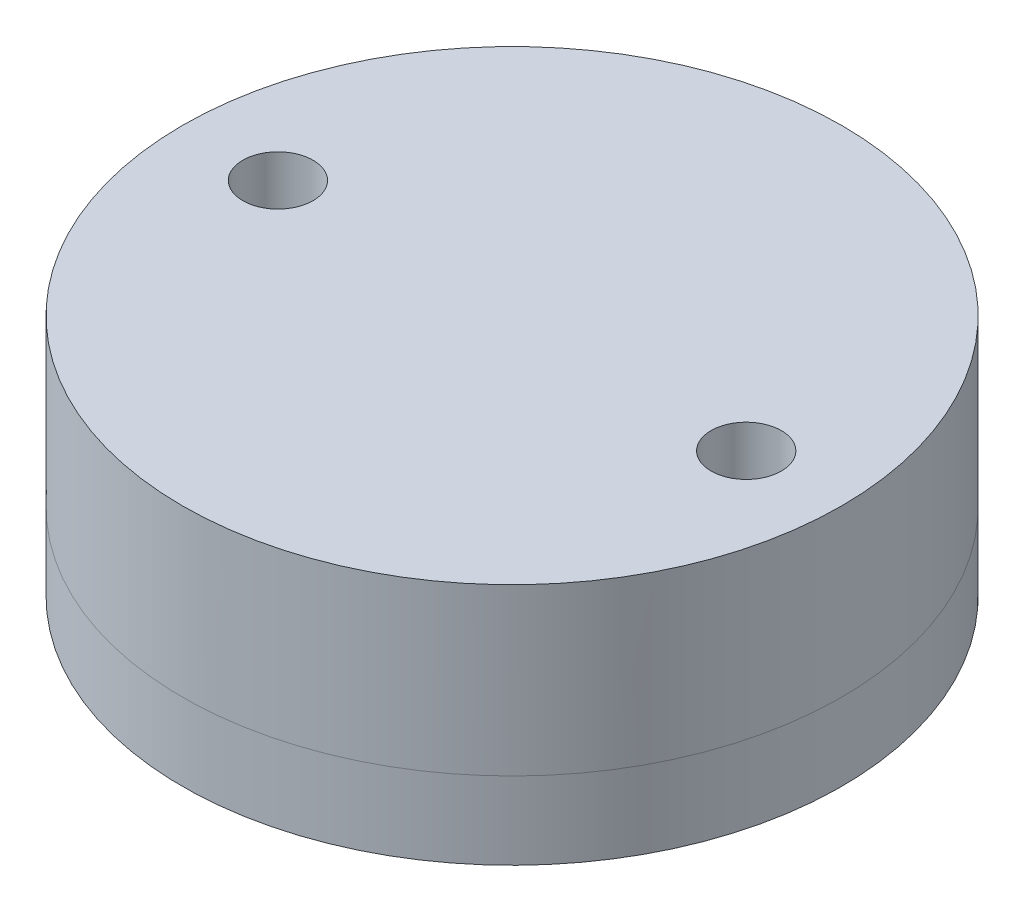
SolidWorks part; units mm, degrees
ref_plane "Front Plane" through (0, 0, 0) normal (0, 0, 1) x (1, 0, 0)
ref_plane "Top Plane" through (0, 0, 0) normal (0, 1, 0) x (1, 0, 0)
ref_plane "Right Plane" through (0, 0, 0) normal (1, 0, 0) x (0, 0, -1)
sketch "Sketch1" plane through (0, 0, 0) normal (0, 0, 1) x (1, 0, 0)
  line L0 (0, 0) -> (0, 14.5) construction
  line L3 (-7.3688, 3.1226) -> (0, 6.425) construction
  line L4 (7.3688, 3.1226) -> (0, 6.425) construction
  line L5 (14.075, 14.5) -> (-14.075, 14.5)
  line L6 (-14.075, 14.5) -> (-14.075, 3.1226)
  line L7 (-14.075, 3.1226) -> (-7.3688, 3.1226)
  line L8 (-8.075, 6.425) -> (-14.075, 6.425)
  line L9 (14.075, 3.1226) -> (7.3688, 3.1226)
  line L10 (8.075, 6.425) -> (14.075, 6.425)
  line L11 (14.075, 14.5) -> (14.075, 3.1226)
  line L12 (-8.075, 6.425) -> (-6.575, 6.425)
  line L13 (8.075, 6.425) -> (6.575, 6.425)
  line L14 (0, 0) -> (0, 14.5)
  circle A3 centre (0, 6.425) radius 6.425
  arc A5 (-6, 3.736) -> (6, 3.736) centre (0, 6.425) cw
  arc A9 (-7.3688, 3.1226) -> (7.3688, 3.1226) centre (0, 6.425) cw
  arc A10 (-3.2202, -0.9801) -> (7.3688, 3.1226) centre (0, 6.425) cw construction
  arc A11 (-2.622, 0.3954) -> (6, 3.736) centre (0, 6.425) cw construction
  arc A12 (-6, 3.736) -> (-7.3688, 3.1226) centre (-6.6844, 3.4293) cw
  arc A13 (6, 3.736) -> (7.3688, 3.1226) centre (6.6844, 3.4293) ccw
  dimension "D1" = 14.5
  dimension "D2" = 1.5
  dimension "D5" = 6
  dimension "D3" = 0.15
  dimension "D4" = 12
revolve "Revolve1" add sketch "Sketch1" angle 360 about L14 region at (-2.7269, 6.425, 0)
revolve "Revolve2" add sketch "Sketch1<3>" angle 360 about L14 region at (9.9985, 10.9631, 0) region at (4.6795, 11.1045, 0)
sketch "Sketch1<3>" plane through (0, 0, 0) normal (0, 0, 1) x (1, 0, 0) same geometry as "Sketch1"
revolve "Revolve3" add sketch "Sketch1<4>" angle 360 about L14 region at (-10.9559, 4.7429, 0) region at (-7.042, 4.6171, 0)
sketch "Sketch1<4>" plane through (0, 0, 0) normal (0, 0, 1) x (1, 0, 0) same geometry as "Sketch1"
sketch "Sketch2" plane through (0, 14.5, 0) normal (0, 1, 0) x (1, 0, 0)
  line L0 (-10, 0) -> (10, 0) construction
  circle A0 centre (-10, 0) radius 1.5
  circle A1 centre (10, 0) radius 1.5
  point P4 (0, 0)
  dimension "D1" = 3
  dimension "D2" = 3
  dimension "D3" = 20
extrude "Cut-Extrude1" cut sketch "Sketch2" against normal blind 25
sketch "Sketch3" plane through (0, 14.5, 0) normal (0, 1, 0) x (1, 0, 0)
  circle A1 centre (0, 0) radius 14.075
  circle A2 centre (0, 0) radius 14.075
  dimension "D1" = 0
extrude "Cut-Extrude2" cut sketch "Sketch3" against normal blind 1
